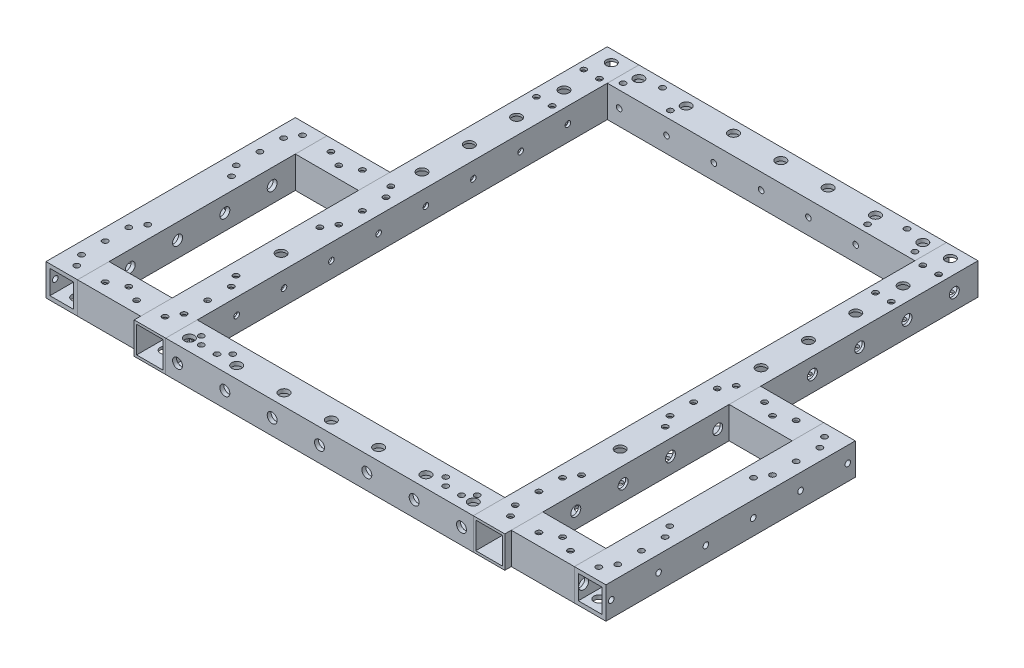
SolidWorks part; units mm, degrees
ref_plane "Front Plane" through (0, 0, 0) normal (0, 0, 1) x (1, 0, 0)
ref_plane "Top Plane" through (0, 0, 0) normal (0, 1, 0) x (1, 0, 0)
ref_plane "Right Plane" through (0, 0, 0) normal (1, 0, 0) x (0, 0, -1)
sketch "Sketch1" plane through (0, 0, 0) normal (0, 0, 1) x (1, 0, 0)
  line L1 (-149.23, -12.7) -> (-123.83, -12.7)
  line L2 (-149.23, -12.7) -> (-149.23, 12.7)
  line L3 (-149.23, 12.7) -> (-123.83, 12.7)
  line L4 (-123.83, -12.7) -> (-123.83, 12.7)
  line L5 (-149.23, -12.7) -> (-123.83, 12.7) construction
  line L6 (-149.23, 12.7) -> (-123.83, -12.7) construction
  line L10 (-147.23, 10.7) -> (-125.83, 10.7)
  line L11 (-125.83, -10.7) -> (-125.83, 10.7)
  line L12 (-147.23, -10.7) -> (-125.83, -10.7)
  line L13 (-147.23, -10.7) -> (-147.23, 10.7)
  line L14 (0, 12.7) -> (0, 0) construction
  line L15 (147.23, 10.7) -> (125.83, 10.7)
  line L16 (125.83, -10.7) -> (125.83, 10.7)
  line L17 (123.83, -12.7) -> (123.83, 12.7)
  line L18 (149.23, -12.7) -> (123.83, -12.7)
  line L19 (147.23, -10.7) -> (125.83, -10.7)
  line L20 (147.23, -10.7) -> (147.23, 10.7)
  line L21 (149.23, -12.7) -> (149.23, 12.7)
  line L22 (149.23, 12.7) -> (123.83, 12.7)
  point P0 (0, 0)
  point P12 (-136.53, 0)
  dimension "D1" = 25.4
  dimension "D2" = 2
  dimension "D3" = 123.83
extrude "Boss-Extrude1" add sketch "Sketch1" along normal blind 105.6 and the other way blind 275.4
sketch "Sketch10" plane through (0, 0, 0) normal (1, 0, 0) x (0, 0, -1)
  line L0 (-105.6, -12.7) -> (275.4, -12.7) construction
  line L1 (250, 12.7) -> (275.4, 12.7)
  line L2 (250, 12.7) -> (250, -12.7)
  line L3 (250, -12.7) -> (275.4, -12.7)
  line L4 (275.4, 12.7) -> (275.4, -12.7)
  line L5 (250, 12.7) -> (275.4, -12.7) construction
  line L6 (250, -12.7) -> (275.4, 12.7) construction
  line L7 (275.4, -12.7) -> (275.4, 12.7) construction
  line L8 (253.175, 9.525) -> (272.225, 9.525)
  line L9 (272.225, 9.525) -> (272.225, -9.525)
  line L10 (253.175, -9.525) -> (272.225, -9.525)
  line L11 (253.175, 9.525) -> (253.175, -9.525)
  line L12 (-105.6, -12.7) -> (-105.6, 12.7) construction
  line L13 (-80.2, -12.7) -> (-105.6, -12.7)
  line L14 (-80.2, -12.7) -> (-80.2, 12.7)
  line L15 (-80.2, 12.7) -> (-105.6, 12.7)
  line L16 (-105.6, -12.7) -> (-105.6, 12.7)
  line L17 (-80.2, -12.7) -> (-105.6, 12.7) construction
  line L18 (-80.2, 12.7) -> (-105.6, -12.7) construction
  line L19 (-105.6, 12.7) -> (275.4, 12.7) construction
  line L20 (-83.375, 9.525) -> (-102.425, 9.525)
  line L21 (-102.425, -9.525) -> (-102.425, 9.525)
  line L22 (-83.375, -9.525) -> (-102.425, -9.525)
  line L23 (-83.375, -9.525) -> (-83.375, 9.525)
  point P0 (262.7, 0)
  point P15 (-92.9, 0)
  dimension "D1" = 3.175
  dimension "D2" = 3.175
extrude "Boss-Extrude4" add sketch "Sketch10" along normal mid plane 247.66 separate body contours L16 L13 L14 L15 L23 L22 L21 L20 region at (0, -12.3408, 92.9)
sketch "Sketch5" plane through (-149.23, 0, 0) normal (-1, 0, 0) x (0, 0, 1)
  line L0 (105.6, 12.7) -> (-275.4, 12.7) construction
  line L1 (-100.4, 12.7) -> (-75, 12.7)
  line L2 (-100.4, 12.7) -> (-100.4, -12.7)
  line L3 (-100.4, -12.7) -> (-75, -12.7)
  line L4 (-75, 12.7) -> (-75, -12.7)
  line L5 (105.6, -12.7) -> (-275.4, -12.7) construction
  line L6 (-75, 0) -> (0, 0) construction
  line L7 (75, 12.7) -> (100.4, 12.7)
  line L8 (75, 12.7) -> (75, -12.7)
  line L9 (75, -12.7) -> (100.4, -12.7)
  line L10 (100.4, 12.7) -> (100.4, -12.7)
  line L11 (0, 0) -> (75, 0) construction
  line L12 (-98.4, 10.7) -> (-77, 10.7)
  line L13 (-77, 10.7) -> (-77, -10.7)
  line L14 (-98.4, -10.7) -> (-77, -10.7)
  line L15 (-98.4, 10.7) -> (-98.4, -10.7)
  line L16 (77, 10.7) -> (98.4, 10.7)
  line L17 (98.4, 10.7) -> (98.4, -10.7)
  line L18 (77, -10.7) -> (98.4, -10.7)
  line L19 (77, 10.7) -> (77, -10.7)
  dimension "D1" = 150
  dimension "D2" = 2
extrude "Boss-Extrude3" add sketch "Sketch5" along normal blind 50.795 separate body
sketch "Sketch11" plane through (0, 0, 0) normal (0, 0, 1) x (1, 0, 0)
  line L0 (-222.25, 9.525) -> (-203.2, 9.525)
  line L1 (-225.425, -12.7) -> (-200.025, -12.7)
  line L2 (-225.425, -12.7) -> (-225.425, 12.7)
  line L3 (-225.425, 12.7) -> (-200.025, 12.7)
  line L4 (-200.025, -12.7) -> (-200.025, 12.7)
  line L5 (-225.425, -12.7) -> (-200.025, 12.7) construction
  line L6 (-225.425, 12.7) -> (-200.025, -12.7) construction
  line L7 (-203.2, -9.525) -> (-203.2, 9.525)
  line L8 (-222.25, -9.525) -> (-203.2, -9.525)
  line L9 (-222.25, -9.525) -> (-222.25, 9.525)
  point P0 (-212.725, 0)
  dimension "D1" = 3.175
extrude "Boss-Extrude5" add sketch "Sketch11" along normal mid plane 200.8 separate body
sketch "Sketch12" plane through (-225.425, 0, 0) normal (-1, 0, 0) x (0, 0, 1)
  line L0 (-100.4, 12.7) -> (-100.4, -12.7) construction
  line L1 (100.4, 12.7) -> (-100.4, 12.7) construction
  circle A0 centre (-94.42, 0) radius 2.25
  circle A1 centre (-56.32, 0) radius 2.25
  circle A2 centre (-18.22, 0) radius 2.25
  circle A3 centre (19.88, 0) radius 2.25
  circle A4 centre (57.98, 0) radius 2.25
  circle A5 centre (96.08, 0) radius 2.25
  dimension "D1" = 5.98
  dimension "D3" = 4.5
  dimension "D2" = 12.7
  dimension "D5" = 38.1
  dimension "D4" = 6
extrude "Cut-Extrude1" cut sketch "Sketch12" against normal blind 10
sketch "Sketch13" plane through (-200.025, 0, 0) normal (1, 0, 0) x (0, 0, -1)
  circle A0 centre (94.42, 0) radius 2.25 construction
  circle A1 centre (94.42, 0) radius 2.25 construction
  circle A2 centre (94.42, 0) radius 4
  circle A3 centre (56.32, 0) radius 4
  circle A4 centre (18.22, 0) radius 4
  circle A5 centre (-19.88, 0) radius 4
  circle A6 centre (-57.98, 0) radius 4
  circle A7 centre (-96.08, 0) radius 4
  dimension "D1" = 8
  dimension "D3" = 38.1
  dimension "D2" = 6
extrude "Cut-Extrude2" cut sketch "Sketch13" against normal blind 10
mirror "Mirror1" about plane through (0, 0, 0) normal (1, 0, 0) of bodies 125 110 109 120
sketch "Sketch14" plane through (0, -12.7, 0) normal (0, -1, 0) x (1, 0, 0)
  line L0 (123.83, 80.2) -> (-123.83, 80.2) construction
  line L2 (-123.83, 105.6) -> (-123.83, -275.4) construction
  circle A0 centre (-114.3, 96.075) radius 2.25
  circle A1 centre (-76.2, 96.075) radius 2.25
  circle A2 centre (-38.1, 96.075) radius 2.25
  circle A3 centre (0, 96.075) radius 2.25
  circle A4 centre (38.1, 96.075) radius 2.25
  circle A5 centre (76.2, 96.075) radius 2.25
  circle A6 centre (114.3, 96.075) radius 2.25
  dimension "D1" = 15.875
  dimension "D3" = 4.5
  dimension "D2" = 9.53
  dimension "D5" = 38.1
  dimension "D4" = 7
extrude "Cut-Extrude3" cut sketch "Sketch14" against normal blind 10
sketch "Sketch15" plane through (0, 12.7, 0) normal (0, 1, 0) x (1, 0, 0)
  line L0 (123.83, -105.6) -> (123.83, 275.4) construction
  line L1 (123.83, -80.2) -> (-123.83, -80.2) construction
  circle A0 centre (114.3, -96.075) radius 4
  circle A1 centre (76.2, -96.075) radius 4
  circle A2 centre (38.1, -96.075) radius 4
  circle A3 centre (0, -96.075) radius 4
  circle A4 centre (-38.1, -96.075) radius 4
  circle A5 centre (-76.2, -96.075) radius 4
  circle A6 centre (-114.3, -96.075) radius 4
  dimension "D1" = 9.53
  dimension "D3" = 8
  dimension "D2" = 15.875
  dimension "D5" = 38.1
  dimension "D4" = 7
extrude "Cut-Extrude4" cut sketch "Sketch15" against normal blind 10
sketch "Sketch9" plane through (0, 0, 0) normal (0, 1, 0) x (1, 0, 0)
  line L0 (-300, 250) -> (-300, -250)
  line L1 (-300, -250) -> (300, -250)
  line L2 (300, -250) -> (300, 250)
  line L3 (300, 250) -> (200, 350)
  line L4 (200, 350) -> (-200, 350)
  line L5 (-200, 350) -> (-300, 250)
  line L6 (0, 350) -> (0, 0) construction
  dimension "D1" = 600
  dimension "D2" = 250
  dimension "D3" = 600
  dimension "D4" = 250
  dimension "D5" = 45
ref_plane "Plane2" through (0, 0, -84.9) normal (0, 0, 1) x (1, 0, 0)
mirror "Mirror3" about plane through (0, 0, -84.9) normal (0, 0, 1) of bodies 127
sketch "Sketch17" plane through (0, 12.7, 0) normal (0, 1, 0) x (1, 0, 0)
  line L0 (174.625, -90.875) -> (174.625, -62.3) construction
  line L1 (174.625, -62.3) -> (133.35, -62.3) construction
  line L2 (123.83, -105.6) -> (123.83, 275.4) construction
  line L3 (200.025, -100.4) -> (149.23, -100.4) construction
  line L4 (200.025, -75) -> (149.23, -75) construction
  circle A0 centre (139.065, -90.875) radius 2.25
  circle A1 centre (133.35, -81.35) radius 2.25
  circle A2 centre (161.925, -90.875) radius 2.25
  circle A3 centre (133.35, -62.3) radius 2.25
  circle A4 centre (187.325, -90.875) radius 2.25
  circle A5 centre (210.185, -90.875) radius 2.25
  circle A6 centre (215.9, -81.35) radius 2.25
  circle A7 centre (215.9, -62.3) radius 2.25
  circle A8 centre (215.9, -43.25) radius 2.25
  circle A9 centre (210.185, -33.725) radius 2.25
  circle A10 centre (139.065, -33.725) radius 2.25
  circle A11 centre (133.35, -43.25) radius 2.25
  circle A12 centre (174.625, -84.53) radius 2.25
  dimension "D1" = 9.52
  dimension "D5" = 4.5
  dimension "D9" = 9.53
  dimension "D2" = 19.05
  dimension "D3" = 9.525
  dimension "D4" = 15.235
  dimension "D6" = 22.86
  dimension "D7" = 19.05
  dimension "D8" = 12.7
extrude "Cut-Extrude5" cut sketch "Sketch17" against normal blind 10
sketch "Sketch18" plane through (0, -12.7, 0) normal (0, -1, 0) x (1, 0, 0)
  line L0 (174.6275, 62.3) -> (133.35, 62.3) construction
  line L4 (174.6275, 62.3) -> (174.6275, 100.4) construction
  line L5 (200.025, 100.4) -> (149.23, 100.4) construction
  circle A0 centre (161.925, 90.875) radius 2.25 construction
  circle A1 centre (139.065, 90.875) radius 2.25 construction
  circle A2 centre (133.35, 81.35) radius 2.25 construction
  circle A3 centre (133.35, 62.3) radius 2.25 construction
  circle A4 centre (161.925, 90.875) radius 2.25 construction
  circle A5 centre (139.065, 90.875) radius 2.25 construction
  circle A6 centre (133.35, 81.35) radius 2.25 construction
  circle A7 centre (133.35, 62.3) radius 2.25 construction
  circle A8 centre (139.065, 90.875) radius 4
  circle A9 centre (133.35, 81.35) radius 4
  circle A10 centre (133.35, 62.3) radius 4
  circle A11 centre (161.925, 90.875) radius 4
  circle A12 centre (215.905, 62.3) radius 4
  circle A13 centre (215.905, 81.35) radius 4
  circle A14 centre (210.19, 90.875) radius 4
  circle A15 centre (187.33, 90.875) radius 4
  circle A16 centre (133.35, 43.25) radius 4
  circle A17 centre (139.065, 33.725) radius 4
  circle A18 centre (210.19, 33.725) radius 4
  circle A19 centre (215.905, 43.25) radius 4
  circle A20 centre (174.625, 84.53) radius 2.25 construction
  circle A21 centre (174.625, 84.53) radius 2.25 construction
  circle A22 centre (174.625, 84.53) radius 4
  dimension "D1" = 8
extrude "Cut-Extrude6" cut sketch "Sketch18" against normal blind 10
mirror "Mirror5" about plane through (0, 0, 0) normal (0, 0, 1) of "Cut-Extrude6", "Cut-Extrude5"
mirror "Mirror6" about plane through (0, 0, 0) normal (1, 0, 0) of "Mirror5", "Cut-Extrude5", "Cut-Extrude6"
sketch "Sketch19" plane through (-123.83, 0, 0) normal (1, 0, 0) x (0, 0, -1)
  line L0 (-86.55, 0) -> (-105.6, 0) construction
  line L1 (-105.6, -12.7) -> (-105.6, 12.7) construction
  line L2 (256.35, 0) -> (275.4, 0) construction
  line L3 (275.4, -12.7) -> (275.4, 12.7) construction
  circle A0 centre (-86.55, 0) radius 2.25
  circle A1 centre (-48.45, 0) radius 2.25
  circle A2 centre (-10.35, 0) radius 2.25
  circle A3 centre (27.75, 0) radius 2.25
  circle A4 centre (65.85, 0) radius 2.25
  circle A5 centre (103.95, 0) radius 2.25
  circle A6 centre (142.05, 0) radius 2.25
  circle A7 centre (180.15, 0) radius 2.25
  circle A8 centre (218.25, 0) radius 2.25
  circle A9 centre (256.35, 0) radius 2.25
  dimension "D1" = 4.5
  dimension "D3" = 38.1
  dimension "D2" = 10
extrude "Cut-Extrude7" cut sketch "Sketch19" against normal blind 10
sketch "Sketch20" plane through (-149.23, 0, 0) normal (-1, 0, 0) x (0, 0, 1)
  circle A0 centre (86.55, 0) radius 2.25 construction
  circle A1 centre (86.55, 0) radius 2.25 construction
  circle A2 centre (86.55, 0) radius 4
  circle A3 centre (48.45, 0) radius 4
  circle A4 centre (10.35, 0) radius 4
  circle A5 centre (-27.75, 0) radius 4
  circle A6 centre (-65.85, 0) radius 4
  circle A7 centre (-103.95, 0) radius 4
  circle A8 centre (-142.05, 0) radius 4
  circle A9 centre (-180.15, 0) radius 4
  circle A10 centre (-218.25, 0) radius 4
  circle A11 centre (-256.35, 0) radius 4
  dimension "D1" = 8
  dimension "D3" = 38.1
  dimension "D2" = 10
extrude "Cut-Extrude8" cut sketch "Sketch20" against normal blind 10
sketch "Sketch21" plane through (123.83, 0, 0) normal (-1, 0, 0) x (0, 0, 1)
  circle A2 centre (-256.35, 0) radius 2.25 construction
  circle A3 centre (-218.25, 0) radius 2.25 construction
  circle A4 centre (-180.15, 0) radius 2.25 construction
  circle A5 centre (-142.05, 0) radius 2.25 construction
  circle A6 centre (-103.95, 0) radius 2.25 construction
  circle A7 centre (-65.85, 0) radius 2.25 construction
  circle A8 centre (-27.75, 0) radius 2.25 construction
  circle A9 centre (10.35, 0) radius 2.25 construction
  circle A10 centre (48.45, 0) radius 2.25 construction
  circle A11 centre (86.55, 0) radius 2.25 construction
  circle A14 centre (-256.35, 0) radius 2.25
  circle A15 centre (-218.25, 0) radius 2.25
  circle A16 centre (-180.15, 0) radius 2.25
  circle A17 centre (-142.05, 0) radius 2.25
  circle A18 centre (-103.95, 0) radius 2.25
  circle A19 centre (-65.85, 0) radius 2.25
  circle A20 centre (-27.75, 0) radius 2.25
  circle A21 centre (10.35, 0) radius 2.25
  circle A22 centre (48.45, 0) radius 2.25
  circle A23 centre (86.55, 0) radius 2.25
extrude "Cut-Extrude9" cut sketch "Sketch21" against normal blind 10
sketch "Sketch22" plane through (149.23, 0, 0) normal (1, 0, 0) x (0, 0, -1)
  circle A0 centre (-86.55, 0) radius 4 construction
  circle A1 centre (-48.45, 0) radius 4 construction
  circle A2 centre (-10.35, 0) radius 4 construction
  circle A3 centre (27.75, 0) radius 4 construction
  circle A4 centre (65.85, 0) radius 4 construction
  circle A5 centre (103.95, 0) radius 4 construction
  circle A6 centre (142.05, 0) radius 4 construction
  circle A7 centre (180.15, 0) radius 4 construction
  circle A8 centre (218.25, 0) radius 4 construction
  circle A9 centre (256.35, 0) radius 4 construction
  circle A12 centre (-86.55, 0) radius 4
  circle A13 centre (-48.45, 0) radius 4
  circle A14 centre (-10.35, 0) radius 4
  circle A15 centre (27.75, 0) radius 4
  circle A16 centre (65.85, 0) radius 4
  circle A17 centre (103.95, 0) radius 4
  circle A18 centre (142.05, 0) radius 4
  circle A19 centre (180.15, 0) radius 4
  circle A20 centre (218.25, 0) radius 4
  circle A21 centre (256.35, 0) radius 4
extrude "Cut-Extrude10" cut sketch "Sketch22" against normal blind 10
sketch "Sketch23" plane through (0, 0, -250) normal (0, 0, 1) x (1, 0, 0)
  line L1 (-114.3, 0) -> (-123.83, 0) construction
  line L2 (-123.83, -12.7) -> (-123.83, 12.7) construction
  line L3 (114.3, 0) -> (123.83, 0) construction
  line L4 (123.83, -12.7) -> (123.83, 12.7) construction
  circle A0 centre (-114.3, 0) radius 2.25
  circle A1 centre (-76.2, 0) radius 2.25
  circle A2 centre (-38.1, 0) radius 2.25
  circle A3 centre (0, 0) radius 2.25
  circle A4 centre (38.1, 0) radius 2.25
  circle A5 centre (76.2, 0) radius 2.25
  circle A6 centre (114.3, 0) radius 2.25
  point P3 (0, 0)
  dimension "D1" = 4.5
  dimension "D2" = 7
  dimension "D3" = 38.1
extrude "Cut-Extrude11" cut sketch "Sketch23" against normal blind 10
sketch "Sketch24" plane through (0, 0, -275.4) normal (0, 0, -1) x (-1, 0, 0)
  circle A0 centre (114.3, 0) radius 2.25 construction
  circle A1 centre (114.3, 0) radius 2.25 construction
  circle A2 centre (114.3, 0) radius 4
  circle A3 centre (76.2, 0) radius 4
  circle A4 centre (38.1, 0) radius 4
  circle A5 centre (0, 0) radius 4
  circle A6 centre (-38.1, 0) radius 4
  circle A7 centre (-76.2, 0) radius 4
  circle A8 centre (-114.3, 0) radius 4
  dimension "D1" = 8
  dimension "D3" = 38.1
  dimension "D2" = 7
extrude "Cut-Extrude12" cut sketch "Sketch24" against normal blind 10
sketch "Sketch25" plane through (0, 0, 80.2) normal (0, 0, -1) x (-1, 0, 0)
  circle A0 centre (114.3, 0) radius 2.25 construction
  circle A1 centre (76.2, 0) radius 2.25 construction
  circle A2 centre (38.1, 0) radius 2.25 construction
  circle A3 centre (0, 0) radius 2.25 construction
  circle A4 centre (-38.1, 0) radius 2.25 construction
  circle A5 centre (-76.2, 0) radius 2.25 construction
  circle A6 centre (-114.3, 0) radius 2.25 construction
  circle A7 centre (114.3, 0) radius 2.25
  circle A8 centre (76.2, 0) radius 2.25
  circle A9 centre (38.1, 0) radius 2.25
  circle A10 centre (0, 0) radius 2.25
  circle A11 centre (-38.1, 0) radius 2.25
  circle A12 centre (-76.2, 0) radius 2.25
  circle A13 centre (-114.3, 0) radius 2.25
extrude "Cut-Extrude13" cut sketch "Sketch25" against normal blind 10
sketch "Sketch26" plane through (0, 0, 105.6) normal (0, 0, 1) x (1, 0, 0)
  circle A0 centre (-114.3, 0) radius 4 construction
  circle A1 centre (-76.2, 0) radius 4 construction
  circle A2 centre (-38.1, 0) radius 4 construction
  circle A3 centre (0, 0) radius 4 construction
  circle A4 centre (38.1, 0) radius 4 construction
  circle A5 centre (76.2, 0) radius 4 construction
  circle A6 centre (114.3, 0) radius 4 construction
  circle A7 centre (-114.3, 0) radius 4
  circle A8 centre (-76.2, 0) radius 4
  circle A9 centre (-38.1, 0) radius 4
  circle A10 centre (0, 0) radius 4
  circle A11 centre (38.1, 0) radius 4
  circle A12 centre (76.2, 0) radius 4
  circle A13 centre (114.3, 0) radius 4
extrude "Cut-Extrude14" cut sketch "Sketch26" against normal blind 10
sketch "Sketch27" plane through (0, -12.7, 0) normal (0, -1, 0) x (1, 0, 0)
  line L0 (136.53, -275.4) -> (136.53, -265.87) construction
  line L1 (123.83, -275.4) -> (149.23, -275.4) construction
  line L2 (0, 0) -> (0, 80.2) construction
  line L3 (123.83, 80.2) -> (-123.83, 80.2) construction
  circle A0 centre (136.53, -113.47) radius 2.25
  circle A1 centre (136.53, -151.57) radius 2.25
  circle A2 centre (136.53, -189.67) radius 2.25
  circle A3 centre (136.53, -227.77) radius 2.25
  circle A4 centre (136.53, 0) radius 2.25
  circle A5 centre (-136.53, -113.47) radius 2.25
  circle A6 centre (-136.53, -151.57) radius 2.25
  circle A7 centre (-136.53, -189.67) radius 2.25
  circle A8 centre (-136.53, -227.77) radius 2.25
  circle A9 centre (-136.53, 0) radius 2.25
  circle A10 centre (136.53, -265.87) radius 2.25
  circle A11 centre (-136.53, -265.87) radius 2.25
  dimension "D1" = 4.5
  dimension "D2" = 5
  dimension "D3" = 38.1
  dimension "D4" = 9.53
sketch "Sketch29" plane through (0, 12.7, 0) normal (0, 1, 0) x (1, 0, 0)
  line L0 (0, 0) -> (0, -80.2) construction
  line L1 (0, 0) -> (0, -80.2) construction
  circle A0 centre (136.53, 0) radius 2.25 construction
  circle A1 centre (136.53, 113.47) radius 2.25 construction
  circle A2 centre (136.53, 0) radius 2.25 construction
  circle A3 centre (136.53, 113.47) radius 2.25 construction
  circle A4 centre (136.53, 113.47) radius 4
  circle A5 centre (136.53, 0) radius 4
  circle A6 centre (136.53, 151.57) radius 4
  circle A7 centre (136.53, 189.67) radius 4
  circle A8 centre (136.53, 227.77) radius 4
  circle A9 centre (-136.53, 0) radius 4
  circle A10 centre (-136.53, 227.77) radius 4
  circle A11 centre (-136.53, 189.67) radius 4
  circle A12 centre (-136.53, 151.57) radius 4
  circle A13 centre (-136.53, 113.47) radius 4
  circle A14 centre (-136.53, 265.87) radius 4
  circle A15 centre (136.53, 265.87) radius 4
  dimension "D1" = 8
  dimension "D3" = 38.1
  dimension "D2" = 4
extrude "Cut-Extrude20" cut sketch "Sketch27" against normal blind 10 contours A4 | A9 region at (136.53, -12.7, 0) region at (-136.53, -12.7, 0)
extrude "Cut-Extrude21" cut sketch "Sketch27<5>" against normal blind 10 contours A0 | A1 | A2 | A3 | A8 | A7 | A6 | A5 | A11 | A10 region at (136.53, -12.7, -113.47) region at (136.53, -12.7, -151.57) region at (136.53, -12.7, -189.67) region at (136.53, -12.7, -227.77) region at (-136.53, -12.7, -113.47) region at (-136.53, -12.7, -151.57) region at (-136.53, -12.7, -189.67) region at (-136.53, -12.7, -227.77) region at (136.53, -12.7, -265.87) region at (-136.53, -12.7, -265.87)
sketch "Sketch27<5>" plane through (0, -12.7, 0) normal (0, -1, 0) x (1, 0, 0) same geometry as "Sketch27"
extrude "Cut-Extrude22" cut sketch "Sketch29" against normal blind 10 contours A5 | A9 region at (136.53, 12.7, 0) region at (-136.53, 12.7, 0)
extrude "Cut-Extrude23" cut sketch "Sketch29<3>" against normal blind 10 contours A4 | A6 | A7 | A8 | A10 | A11 | A12 | A13 | A14 | A15 region at (136.53, 12.7, -113.47) region at (136.53, 12.7, -151.57) region at (136.53, 12.7, -189.67) region at (136.53, 12.7, -227.77) region at (-136.53, 12.7, -227.77) region at (-136.53, 12.7, -189.67) region at (-136.53, 12.7, -151.57) region at (-136.53, 12.7, -113.47) region at (-136.53, 12.7, -265.87) region at (136.53, 12.7, -265.87)
sketch "Sketch29<3>" plane through (0, 12.7, 0) normal (0, 1, 0) x (1, 0, 0) same geometry as "Sketch29"
sketch "Sketch31" plane through (0, 12.7, 0) normal (0, 1, 0) x (1, 0, 0)
  line L0 (149.23, 275.4) -> (123.83, 275.4) construction
  line L1 (142.88, 211.9) -> (130.18, 211.9) construction
  line L2 (142.88, 211.9) -> (142.88, 250) construction
  line L3 (142.88, 250) -> (130.18, 250) construction
  line L4 (130.18, 211.9) -> (130.18, 250) construction
  line L5 (142.88, 211.9) -> (130.18, 250) construction
  line L6 (142.88, 250) -> (130.18, 211.9) construction
  line L7 (149.23, 275.4) -> (149.23, -105.6) construction
  line L8 (123.83, 275.4) -> (123.83, -105.6) construction
  line L9 (79.38, 256.35) -> (117.48, 256.35) construction
  line L10 (98.43, 269.05) -> (98.43, 256.35) construction
  line L11 (123.83, 250) -> (-123.83, 250) construction
  line L12 (123.83, 275.4) -> (-123.83, 275.4) construction
  line L13 (0, 0) -> (0, 250) construction
  circle A0 centre (130.18, 250) radius 2.25
  circle A1 centre (142.88, 250) radius 2.25
  circle A2 centre (130.18, 211.9) radius 2.25
  circle A3 centre (142.88, 211.9) radius 2.25
  circle A4 centre (79.38, 256.35) radius 2.25
  circle A5 centre (117.48, 256.35) radius 2.25
  circle A6 centre (98.43, 269.05) radius 2.25
  circle A7 centre (-142.88, 211.9) radius 2.25
  circle A8 centre (-130.18, 211.9) radius 2.25
  circle A9 centre (-130.18, 250) radius 2.25
  circle A10 centre (-142.88, 250) radius 2.25
  circle A11 centre (-117.48, 256.35) radius 2.25
  circle A12 centre (-98.43, 269.05) radius 2.25
  circle A13 centre (-79.38, 256.35) radius 2.25
  point P0 (136.53, 230.95)
  dimension "D1" = 4.5
  dimension "D6" = 31.75
  dimension "D8" = 38.1
  dimension "D2" = 25.4
  dimension "D3" = 38.1
  dimension "D4" = 6.35
  dimension "D5" = 6.35
  dimension "D7" = 6.35
  dimension "D9" = 6.35
extrude "Cut-Extrude25" cut sketch "Sketch31" against normal blind 10
sketch "Sketch32" plane through (0, 12.7, 0) normal (0, 1, 0) x (1, 0, 0)
  line L0 (123.83, -80.2) -> (123.83, -105.6) construction
  line L1 (123.83, -80.2) -> (-123.83, -80.2) construction
  line L2 (123.83, -105.6) -> (-123.83, -105.6) construction
  line L3 (123.83, 275.4) -> (123.83, -105.6) construction
  line L4 (0, 0) -> (0, -80.2) construction
  circle A0 centre (111.125, -89.725) radius 2.25
  circle A1 centre (104.775, -96.07) radius 2.25
  circle A2 centre (92.075, -96.07) radius 2.25
  circle A3 centre (85.725, -89.725) radius 2.25
  circle A4 centre (-85.725, -89.725) radius 2.25
  circle A5 centre (-92.075, -96.07) radius 2.25
  circle A6 centre (-104.775, -96.07) radius 2.25
  circle A7 centre (-111.125, -89.725) radius 2.25
  dimension "D1" = 12.705
  dimension "D5" = 4.5
  dimension "D2" = 9.525
  dimension "D3" = 9.53
  dimension "D4" = 19.055
  dimension "D6" = 12.7
  dimension "D7" = 25.4
extrude "Cut-Extrude26" cut sketch "Sketch32" against normal blind 10
